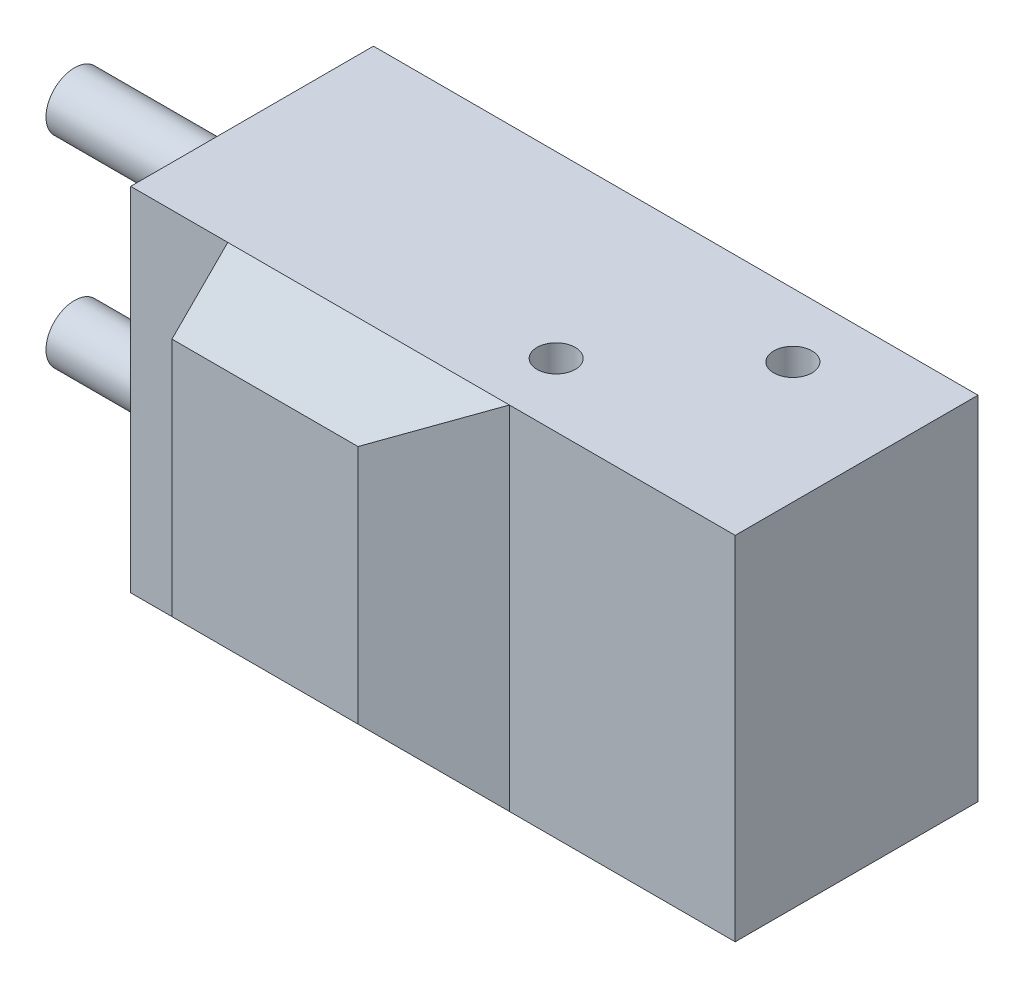
SolidWorks part; units mm, degrees
ref_plane "Front" through (0, 0, 0) normal (0, 0, 1) x (1, 0, 0)
ref_plane "Top" through (0, 0, 0) normal (0, 1, 0) x (1, 0, 0)
ref_plane "Right" through (0, 0, 0) normal (1, 0, 0) x (0, 0, -1)
sketch "Sketch1" plane through (0, 0, 0) normal (0, 0, 1) x (1, 0, 0)
  line L1 (0, 0) -> (63.246, 0)
  line L2 (0, 0) -> (0, 36.83)
  line L3 (0, 36.83) -> (63.246, 36.83)
  line L4 (63.246, 0) -> (63.246, 36.83)
  dimension "D1" = 63.246
  dimension "D2" = 36.83
extrude "Extrude1" add sketch "Sketch1" along normal blind 25.4
hole_wizard "M4x0.7 Tapped Hole1" positions "Sketch3" profile "Sketch2" tap size "M4x0.7" standard "Ansi Metric"
sketch "Sketch3" plane through (0, 0, 0) normal (0, -1, 0) x (1, 0, 0)
  line L0 (63.246, 25.4) -> (63.246, 0) construction
  line L1 (0, 25.4) -> (63.246, 25.4) construction
  point P0 (37.846, 6.6675)
  point P1 (50.546, 18.7325)
  dimension "D1" = 12.7
  dimension "D2" = 25.4
  dimension "D3" = 6.6675
  dimension "D4" = 12.065
sketch "Sketch2" plane through (37.846, 0, 6.6675) normal (1, 0, 0) x (0, 0, -1)
  line L0 (0, 0) -> (0, 6.0714)
  line L1 (0, 6.0714) -> (1.65, 5.08)
  line L2 (1.65, 5.08) -> (1.65, 8)
  line L3 (1.65, 8) -> (2, 8)
  line L4 (2, 8) -> (2, 0)
  line L5 (2, 0) -> (0, 0)
  line L10 (0, 6.0714) -> (-1.65, 5.08) construction
  line L11 (0, -6.35) -> (0, 107.95) construction
  dimension "Tap Drill Dia." = 3.3
  dimension "Tap Drill Depth" = 5.08
  dimension "Thread Major Dia." = 4
  dimension "Thread Depth" = 8
  dimension "Drill Angle" = 118
hole_wizard "M4x0.7 Tapped Hole2" positions "Sketch4" profile "Sketch5" tap size "M4x0.7" standard "Ansi Metric"
sketch "Sketch4" plane through (53.4706, 36.83, -0.6208) normal (0, 1, 0) x (-1, 0, 0)
  line L2 (-9.7754, 0.6208) -> (53.4706, 0.6208) construction
  line L3 (-9.7754, 26.0208) -> (53.4706, 26.0208) construction
  line L4 (-9.7754, 26.0208) -> (-9.7754, 0.6208) construction
  point P0 (2.9246, 7.2883)
  point P1 (15.6246, 19.3533)
  dimension "D1" = 6.6675
  dimension "D2" = 6.6675
  dimension "D3" = 12.7
  dimension "D4" = 12.065
  dimension "D5" = 25.4
sketch "Sketch5" plane through (50.546, 36.83, 6.6675) normal (1, 0, 0) x (0, 0, 1)
  line L0 (0, 0) -> (0, 6.0714)
  line L1 (0, 6.0714) -> (1.65, 5.08)
  line L2 (1.65, 5.08) -> (1.65, 8)
  line L3 (1.65, 8) -> (2, 8)
  line L4 (2, 8) -> (2, 0)
  line L5 (2, 0) -> (0, 0)
  line L10 (0, 6.0714) -> (-1.65, 5.08) construction
  line L11 (0, -6.35) -> (0, 107.95) construction
  dimension "Tap Drill Dia." = 3.3
  dimension "Tap Drill Depth" = 5.08
  dimension "Thread Major Dia." = 4
  dimension "Thread Depth" = 8
  dimension "Drill Angle" = 118
sketch "Sketch6" plane through (0, 0, 25.4) normal (0, 0, 1) x (1, 0, 0)
  line L0 (0, 0) -> (63.246, 0) construction
  line L1 (10.16, 0) -> (39.624, 0)
  line L2 (10.16, 0) -> (10.16, 36.83)
  line L3 (10.16, 36.83) -> (39.624, 36.83)
  line L4 (39.624, 0) -> (39.624, 36.83)
  line L6 (0, 36.83) -> (0, 0) construction
  line L8 (63.246, 0) -> (63.246, 36.83) construction
  dimension "D1" = 10.16
  dimension "D2" = 23.622
extrude "Extrude2" add sketch "Sketch6" along normal blind 5.842
chamfer "Chamfer1" distance 5.842 angle 45 1 edges at (24.892, 0, 31.242)
chamfer "Chamfer2" distance 5.842 angle 45 1 edges at (24.892, 36.83, 31.242)
chamfer "Chamfer3" distance 5.842 distance2 10 1 edges at (39.624, 18.415, 31.242) first distance on face at (39.624, 15.2718, 28.321)
sketch "Sketch7" plane through (0, 0, 0) normal (-1, 0, 0) x (0, 0, 1)
  line L4 (25.4, 36.83) -> (0, 36.83) construction
  line L5 (12.7, 36.83) -> (12.7, 0) construction
  line L6 (25.4, 0) -> (0, 0) construction
  line L7 (0, 18.415) -> (25.4, 18.415) construction
  line L8 (25.4, 36.83) -> (25.4, 0) construction
  line L9 (0, 36.83) -> (0, 0) construction
  circle A0 centre (12.7, 28.956) radius 2.9782
  circle A1 centre (12.7, 7.874) radius 2.9781
  dimension "D3" = 5.9563
  dimension "D4" = 5.9563
  dimension "D1" = 10.541
  dimension "D2" = 10.541
extrude "Extrude3" add sketch "Sketch7" along normal blind 18.5801
